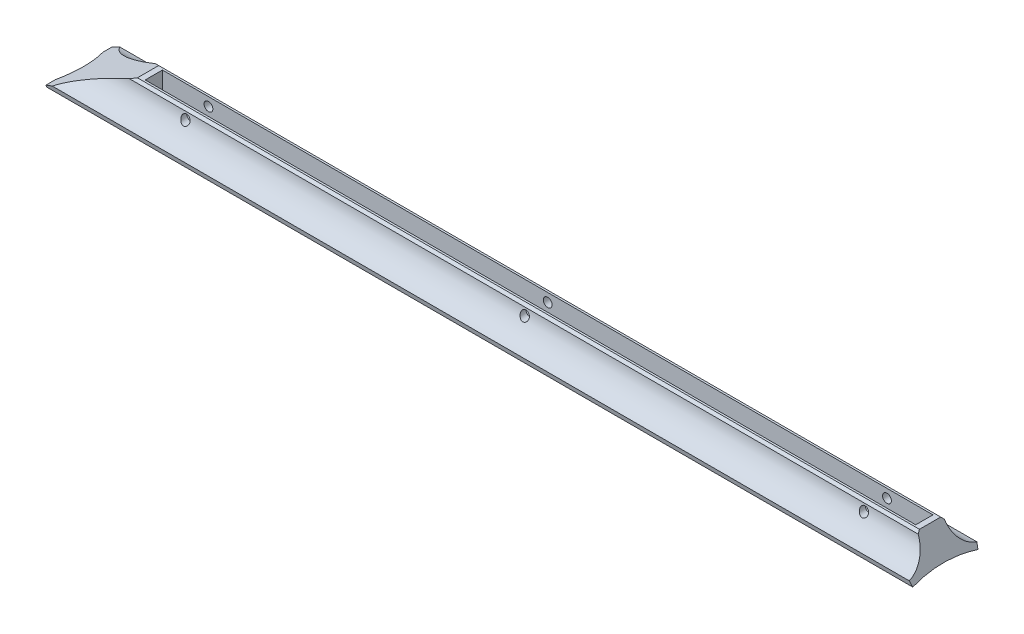
SolidWorks part; units mm, degrees
material "6061-T6 (SS)"
ref_plane "Front Plane" through (0, 0, 0) normal (0, 0, 1) x (1, 0, 0)
ref_plane "Top Plane" through (0, 0, 0) normal (0, 1, 0) x (1, 0, 0)
ref_plane "Right Plane" through (0, 0, 0) normal (1, 0, 0) x (0, 0, -1)
ref_plane "Plane4" through (0, 0, 44.945) normal (0, 0, 1) x (1, 0, 0)
sketch "Sketch1" plane through (0, 0, 0) normal (1, 0, 0) x (0, 0, -1)
  line L0 (-38.1, -12.7) -> (-38.1, -9.525)
  line L1 (38.1, -12.7) -> (-38.1, -12.7) construction
  line L2 (38.1, -12.7) -> (38.1, 12.7) construction
  line L3 (38.1, 12.7) -> (-38.1, 12.7) construction
  line L4 (-38.1, -12.7) -> (-38.1, 12.7) construction
  line L5 (9.1147, -3.0382) -> (-38.1, 12.7) construction
  line L6 (38.1, 12.7) -> (-38.1, -12.7) construction
  line L7 (38.1, -12.7) -> (38.1, -9.525)
  line L8 (-7.1374, 12.7) -> (7.1374, 12.7)
  line L9 (-18.661, -1.9622) -> (-18.0075, -4.6495)
  line L10 (18.661, -1.9622) -> (18.0075, -4.6495)
  arc A0 (-18.0075, -4.6495) -> (18.0075, -4.6495) centre (0, -78.6911) cw
  arc A2 (-7.1374, 12.7) -> (-18.661, -1.9622) centre (-22.227, 12.7) cw
  arc A3 (7.1374, 12.7) -> (18.661, -1.9622) centre (22.227, 12.7) ccw
  arc A5 (-0.8109, 0.2703) -> (0.8109, 0.2703) centre (0, -78.6911) cw
  point P0 (0, 0)
  point P12 (0, 12.7)
  dimension "D3" = 76.2
  dimension "D1" = 76.2
  dimension "D2" = 25.4
  dimension "D4" = 3.175
  dimension "D5" = 14.2748
extrude "Boss-Extrude1" add sketch "Sketch1" along normal mid plane 508 contours A3 L8 A2 L0 A0 L7 region at (0, 3.2534, 0)
sketch "Sketch2" plane through (0, 0, 44.945) normal (0, 0, 1) x (1, 0, 0)
  line L0 (-254, 12.7) -> (-215.9, 12.7)
  line L1 (254, 12.7) -> (-254, 12.7) construction
  line L2 (-254, 12.7) -> (-254, -3.6322)
  line L3 (254, -4.6495) -> (-254, -4.6495) construction
  line L4 (-254, -3.6322) -> (-215.9, 12.7)
  line L5 (254, -4.6495) -> (224.3582, -4.6495)
  line L7 (254, 12.7) -> (215.9, 12.7)
  line L8 (215.9, 12.7) -> (224.3582, -4.6495)
  line L9 (254, 12.7) -> (254, -4.6495)
  dimension "D1" = 38.1
  dimension "D2" = 16.3322
  dimension "D3" = 29.6418
  dimension "D4" = 38.1
extrude "Cut-Extrude1" cut sketch "Sketch2" against normal through all
sketch "Sketch3" plane through (0, 12.7, 0) normal (0, 1, 0) x (1, 0, 0)
  line L1 (215.9, 0) -> (212.725, 0) construction
  line L2 (-212.725, 4.7625) -> (212.725, 4.7625)
  line L3 (-212.725, 4.7625) -> (-212.725, -4.7625)
  line L4 (-212.725, -4.7625) -> (212.725, -4.7625)
  line L5 (212.725, 4.7625) -> (212.725, -4.7625)
  line L6 (-212.725, 4.7625) -> (212.725, -4.7625) construction
  line L7 (-212.725, -4.7625) -> (212.725, 4.7625) construction
  line L8 (215.9, 7.1374) -> (215.9, -7.1374) construction
  point P3 (0, 0)
  dimension "D1" = 3.175
  dimension "D2" = 9.525
extrude "Cut-Extrude2" cut sketch "Sketch3" against normal blind 9.525
sketch "Sketch6" plane through (0, 0, -4.7625) normal (0, 0, 1) x (1, 0, 0)
  line L0 (-212.725, 7.9375) -> (-187.325, 7.9375) construction
  line L1 (-212.725, 3.175) -> (-212.725, 12.7) construction
  line L2 (212.725, 7.9375) -> (187.325, 7.9375) construction
  line L3 (212.725, 3.175) -> (212.725, 12.7) construction
  line L4 (212.725, 12.7) -> (-212.725, 12.7) construction
  line L5 (-212.725, 7.9375) -> (212.725, 7.9375) construction
  line L6 (0, 7.9375) -> (0, 12.7) construction
  circle A0 centre (-187.325, 7.9375) radius 2.4384
  circle A1 centre (187.325, 7.9375) radius 2.4384
  circle A2 centre (0, 7.9375) radius 2.4384
  point P4 (-212.725, 7.9375)
  dimension "D2" = 4.8768
  dimension "D4" = 4.8768
  dimension "D5" = 4.8768
  dimension "D1" = 25.4
  dimension "D3" = 25.4
extrude "Cut-Extrude3" cut sketch "Sketch6" against normal up to surface and the other way up to surface up to face at (-7.6836, 4.3723, -11.6312) other way up to face at (-7.6836, 4.3723, 11.6312)
ref_plane "Plane1" through (212.725, 12.7, 4.7625) normal (0, 0, -1) x (-1, 0, 0)
chamfer "Chamfer1" distance 1.27 angle 45 2 edges at (0, 12.7, -7.1374) (0, 12.7, 7.1374)
